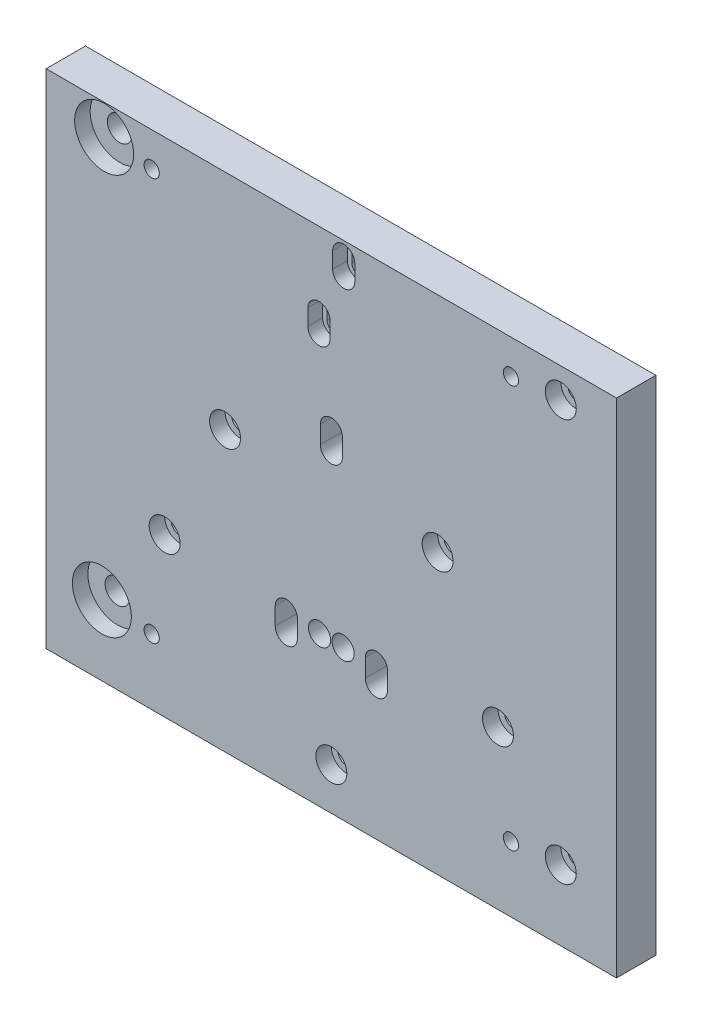
SolidWorks part; units mm, degrees
material "Beech"
ref_plane "Front Plane" through (0, 0, 0) normal (0, 0, 1) x (1, 0, 0)
ref_plane "Top Plane" through (0, 0, 0) normal (0, 1, 0) x (1, 0, 0)
ref_plane "Right Plane" through (0, 0, 0) normal (1, 0, 0) x (0, 0, -1)
sketch "Sketch1" plane through (0, 0, 0) normal (0, 0, 1) x (1, 0, 0)
  line L1 (2.065, -202.025) -> (-182.085, -202.025)
  line L2 (2.065, -202.025) -> (2.065, -55.975)
  line L3 (2.065, -55.975) -> (-182.085, -55.975)
  line L4 (-182.085, -202.025) -> (-182.085, -55.975)
  line L5 (2.065, -202.025) -> (-182.085, -55.975) construction
  line L6 (2.065, -55.975) -> (-182.085, -202.025) construction
  point P0 (-90.01, -129)
  dimension "D1" = 184.15
  dimension "D2" = 146.05
extrude "Boss-Extrude1" add sketch "Sketch1" along normal blind 12.7
ref_plane "CL" through (0, -129, 0) normal (0, -1, 0) x (-1, 0, 0)
sketch "Sketch5" plane through (0, -202.025, 0) normal (0, -1, 0) x (1, 0, 0)
  line L4 (-182.085, 0) -> (2.065, 0)
  line L5 (2.065, 0) -> (2.065, 12.7)
  line L6 (2.065, 12.7) -> (-182.085, 12.7)
  line L7 (-182.085, 12.7) -> (-182.085, 0)
  line L8 (-182.085, 0) -> (2.065, 0)
  line L9 (2.065, 0) -> (2.065, 12.7)
  line L10 (2.065, 12.7) -> (-182.085, 12.7)
  line L11 (-182.085, 12.7) -> (-182.085, 0)
  dimension "D1" = 0
extrude "Boss-Extrude2" add sketch "Sketch5" along normal up to surface (16.125 mm away)
hole_wizard "CBORE for M5 SHCS2" positions "Sketch2" profile "Sketch3" counterbore size "M5" standard "ANSI Metric" end condition up to next
sketch "Sketch2" plane through (0, 0, 12.7) normal (0, 0, 1) x (1, 0, 0)
  point P0 (-55.7, -127.9887)
  point P2 (-124.32, -127.9887)
  point P17 (-90.01, -204.5313)
  point P19 (-143.8109, -167.1)
  point P21 (-36.2091, -167.1)
sketch "Sketch3" plane through (-55.7, -127.9887, 12.7) normal (1, 0, 0) x (0, -1, 0)
  line L0 (0, 0) -> (0, 12.7)
  line L1 (0, 12.7) -> (2.9, 12.7)
  line L3 (2.9, 12.7) -> (2.9, 5)
  line L4 (2.9, 5) -> (5, 5)
  line L5 (5, 5) -> (5, 0)
  line L7 (5, 0) -> (0, 0)
  line L11 (0, -6.35) -> (0, 107.95) construction
  dimension "Thru Hole Dia." = 5.8
  dimension "Thru Hole Depth" = 12.7
  dimension "C'Bore Dia." = 10
  dimension "C'Bore Depth" = 5
hole_wizard "CBORE for M5 SHCS3" positions "Sketch6" profile "Sketch7" counterbore size "M5" standard "ANSI Metric" end condition through all
sketch "Sketch6" plane through (0, 0, 12.7) normal (0, 0, 1) x (1, 0, 0)
  point P0 (-15.925, -65.5)
  point P2 (-15.925, -195.4887)
  point P4 (-164.095, -195.4887)
  point P6 (-163.361, -65.7922)
sketch "Sketch7" plane through (-15.925, -65.5, 12.7) normal (1, 0, 0) x (0, -1, 0)
  line L0 (0, 0) -> (0, 12.7)
  line L1 (0, 12.7) -> (2.65, 12.7)
  line L3 (2.65, 12.7) -> (2.65, 5)
  line L4 (2.65, 5) -> (5, 5)
  line L5 (5, 5) -> (5, 0)
  line L7 (5, 0) -> (0, 0)
  line L11 (0, -6.35) -> (0, 107.95) construction
  dimension "Thru Hole Dia." = 5.3
  dimension "Thru Hole Depth" = 12.7
  dimension "C'Bore Dia." = 10
  dimension "C'Bore Depth" = 5
sketch "Sketch12" plane through (0, 0, 0) normal (0, 0, -1) x (-1, 0, 0)
  circle A0 centre (164.095, -65.5) radius 5
  circle A1 centre (164.095, -196.2787) radius 5
  dimension "D1" = 10
hole_wizard "CBORE SLOT for #6 Socket Head Cap Screw1" positions "Sketch15" profile "Sketch16" size "#6" standard "ANSI Inch" slot yes end condition through all
sketch "Sketch15" plane through (0, 0, 12.7) normal (0, 0, 1) x (1, 0, 0)
  line L0 (-90.01, -118.7375) -> (-90.01, -109.2125) construction
  line L1 (-90.01, -218.15) -> (-90.01, -55.975) construction
  line L2 (-182.085, -218.15) -> (2.065, -218.15) construction
  line L3 (2.065, -55.975) -> (-182.085, -55.975) construction
  point P0 (-90.01, -113.975)
  point P6 (-104.5514, -171.9951)
  point P17 (-75.4686, -171.9951)
  point P18 (0, 0)
  dimension "D1" = 9.525
sketch "Sketch16" plane through (-90.01, -113.975, 12.7) normal (1, 0, 0) x (0, -1, 0)
  line L0 (0, 0) -> (0, 12.7)
  line L1 (0, 12.7) -> (1.8986, 12.7)
  line L3 (1.8986, 12.7) -> (1.8986, 7.3152)
  line L4 (1.8986, 7.3152) -> (3.5725, 7.3152)
  line L5 (3.5725, 7.3152) -> (3.5725, 0)
  line L7 (3.5725, 0) -> (0, 0)
  line L11 (0, -6.35) -> (0, 107.95) construction
  dimension "Thru Hole Dia." = 3.7973
  dimension "Thru Hole Depth" = 12.7
  dimension "C'Bore Dia." = 7.145
  dimension "C'Bore Depth" = 7.3152
hole_wizard "CBORE for #6 Socket Head Cap Screw1" positions "Sketch19" profile "Sketch18" counterbore size "#6" standard "ANSI Inch" end condition through all
sketch "Sketch19" plane through (0, 0, 12.7) normal (0, 0, 1) x (1, 0, 0)
  line L0 (-90.01, -218.15) -> (-90.01, -55.975) construction
  line L1 (-182.085, -218.15) -> (2.065, -218.15) construction
  line L2 (2.065, -55.975) -> (-182.085, -55.975) construction
  point P0 (-93.82, -169.8501)
  point P15 (-86.2, -169.8501)
  dimension "D1" = 48.2999
  dimension "D2" = 3.81
sketch "Sketch18" plane through (-93.82, -169.8501, 12.7) normal (1, 0, 0) x (0, -1, 0)
  line L0 (0, 0) -> (0, 12.7)
  line L1 (0, 12.7) -> (2.1526, 12.7)
  line L3 (2.1526, 12.7) -> (2.1526, 7.3152)
  line L4 (2.1526, 7.3152) -> (3.5725, 7.3152)
  line L5 (3.5725, 7.3152) -> (3.5725, 0)
  line L7 (3.5725, 0) -> (0, 0)
  line L11 (0, -6.35) -> (0, 107.95) construction
  dimension "Thru Hole Dia." = 4.3053
  dimension "Thru Hole Depth" = 12.7
  dimension "C'Bore Dia." = 7.145
  dimension "C'Bore Depth" = 7.3152
hole_wizard "#8 Clearance Hole1" positions "Sketch20" profile "Sketch21" hole size "#8" standard "ANSI Inch" end condition through all
sketch "Sketch20" plane through (0, 0, 12.7) normal (0, 0, 1) x (1, 0, 0)
  point P0 (-32.01, -66.9887)
  point P4 (-148.01, -66.9887)
  point P6 (-148.01, -196.9887)
  point P8 (-32.01, -196.9887)
sketch "Sketch21" plane through (-32.01, -66.9887, 12.7) normal (1, 0, 0) x (0, -1, 0)
  line L0 (0, 0) -> (0, 12.7)
  line L1 (0, 12.7) -> (2.4574, 12.7)
  line L2 (2.4574, 12.7) -> (2.4574, 0)
  line L5 (2.4574, 0) -> (0, 0)
  line L11 (0, -6.35) -> (0, 107.95) construction
  dimension "Thru Hole Dia." = 4.9149
  dimension "Thru Hole Depth" = 12.7
hole_wizard "CBORE SLOT for #6 Socket Head Cap Screw2" positions "Sketch22" profile "Sketch23" size "#6" standard "ANSI Inch" slot yes end condition through all
sketch "Sketch22" plane through (0, 0, 12.7) normal (0, 0, 1) x (1, 0, 0)
  line L0 (-94.01, -87.9375) -> (-94.01, -78.4125) construction
  point P0 (-94.01, -83.175)
  point P2 (-86.01, -63.175)
  point P13 (-86.01, -63.175)
  point P14 (-94.01, -83.175)
  point P15 (-97.2693, -70.3837)
  point P16 (-94.01, -83.175)
  point P17 (-94.01, -83.175)
  point P18 (-86.01, -63.175)
  dimension "D1" = 9.525
sketch "Sketch23" plane through (-94.01, -83.175, 12.7) normal (1, 0, 0) x (0, -1, 0)
  line L0 (0, 0) -> (0, 12.7)
  line L1 (0, 12.7) -> (2.1527, 12.7)
  line L3 (2.1527, 12.7) -> (2.1526, 4.7752)
  line L4 (2.1526, 4.7752) -> (3.5725, 4.7752)
  line L5 (3.5725, 4.7752) -> (3.5725, 0)
  line L7 (3.5725, 0) -> (0, 0)
  line L11 (0, -6.35) -> (0, 107.95) construction
  dimension "Thru Hole Dia." = 4.3053
  dimension "Thru Hole Depth" = 12.7
  dimension "C'Bore Dia." = 7.145
  dimension "C'Bore Depth" = 4.7752
sketch "Sketch24" plane through (0, 0, 0) normal (0, 0, -1) x (-1, 0, 0)
  circle A0 centre (148.01, -66.9887) radius 9.525
  circle A1 centre (32.01, -66.9887) radius 9.525
  circle A2 centre (32.01, -196.9887) radius 9.525
  circle A3 centre (148.01, -196.9887) radius 9.525
  dimension "D1" = 19.05
extrude "Cut-Extrude2" cut sketch "Sketch24" against normal blind 3.175
sketch "Sketch25" plane through (0, 0, 12.7) normal (0, 0, 1) x (1, 0, 0)
  circle A0 centre (-163.361, -65.7922) radius 3.9687
  circle A1 centre (-164.095, -195.4887) radius 3.9687
  circle A2 centre (-164.095, -195.4887) radius 5 construction
  dimension "D1" = 7.9375
extrude "Cut-Extrude3" cut sketch "Sketch25" against normal up to next
sketch "Sketch26" plane through (0, 0, 12.7) normal (0, 0, 1) x (1, 0, 0)
  circle A0 centre (-164.095, -195.4887) radius 9.525
  circle A1 centre (-163.361, -65.7922) radius 9.525
  circle A3 centre (-163.361, -65.7922) radius 5 construction
  dimension "D1" = 19.05
extrude "Cut-Extrude4" cut sketch "Sketch26" against normal up to surface (5 mm away) up to face at (-168.0638, -195.4887, 7.7)
